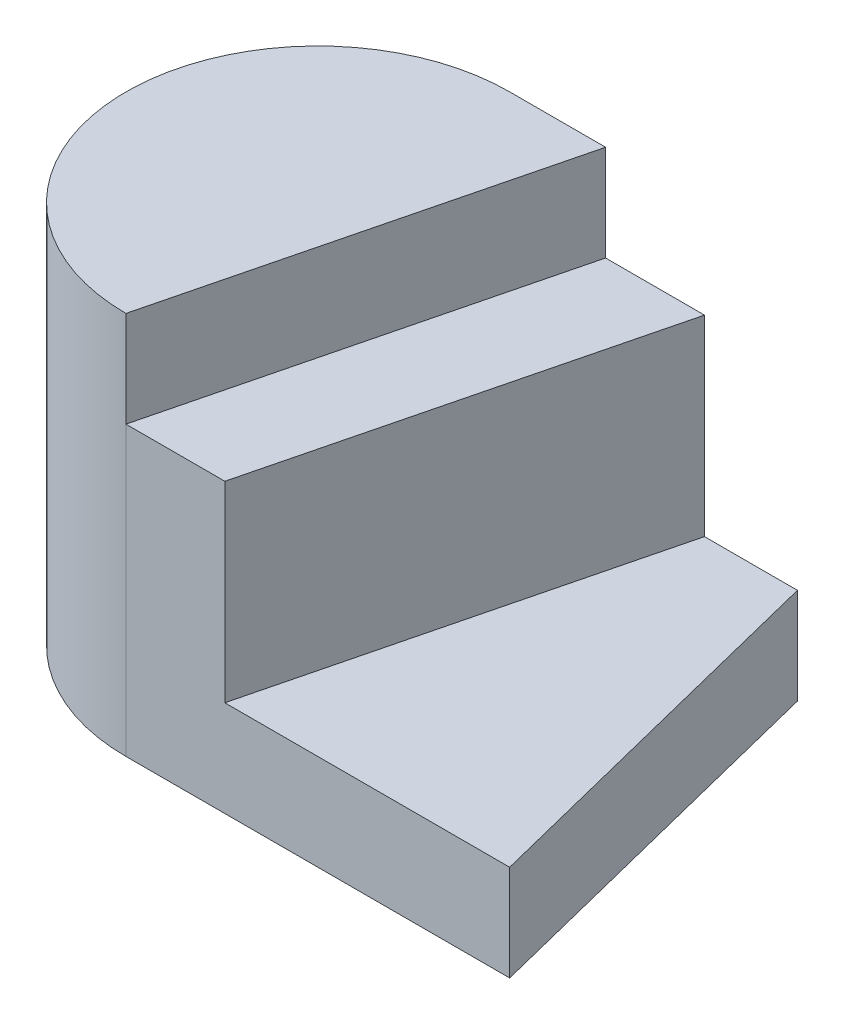
SolidWorks part; units mm, degrees
ref_plane "前基準面" through (0, 0, 0) normal (0, 0, 1) x (1, 0, 0)
ref_plane "上基準面" through (0, 0, 0) normal (0, 1, 0) x (1, 0, 0)
ref_plane "右基準面" through (0, 0, 0) normal (1, 0, 0) x (0, 0, -1)
sketch "草圖1" plane through (0, 0, 0) normal (0, 1, 0) x (1, 0, 0)
  line L0 (0, -20) -> (40, -20)
  line L1 (40, -20) -> (30, 20)
  line L2 (30, 20) -> (0, 20)
  arc A0 (0, 20) -> (0, -20) centre (0, 0) ccw
  dimension "D3" = 20
  dimension "D1" = 30
  dimension "D2" = 40
extrude "填料-伸長1" add sketch "草圖1" against normal blind 10
sketch "草圖2" plane through (0, 0, 0) normal (0, 1, 0) x (1, 0, 0)
  line L0 (0, 20) -> (10, 20)
  line L1 (30, 20) -> (0, 20) construction
  line L2 (10, 20) -> (0, -20)
  line L3 (20.3078, 20) -> (10.3078, -20)
  line L5 (10, 20) -> (20.3078, 20)
  line L6 (0, -20) -> (10.3078, -20)
  line L7 (0, -20) -> (40, -20) construction
  line L8 (22.8078, 30) -> (8.0853, -28.8899) construction
  line L9 (0, 30) -> (22.8078, 30) construction
  arc A0 (0, 20) -> (0, -20) centre (0, 0) ccw
  arc A2 (0, 30) -> (8.0853, -28.8899) centre (0, 0) ccw construction
  arc M2 (0, 20) -> (0, -20) centre (0, 0) ccw
  line M3 (0, -20) -> (40, -20)
  line M5 (30, 20) -> (0, 20)
  dimension "D1" = 10
  dimension "D2" = 10
extrude "填料-伸長2" add sketch "草圖2" along normal blind 30 contours L2 M5 M2 region at (-5.6339, 0, -1.6097)
extrude "填料-伸長3" add sketch "草圖2<3>" along normal blind 20 contours L3 L2 M5 M3 region at (10.1539, 0, 0)
sketch "草圖2<3>" plane through (0, 0, 0) normal (0, 1, 0) x (1, 0, 0) same geometry as "草圖2"
